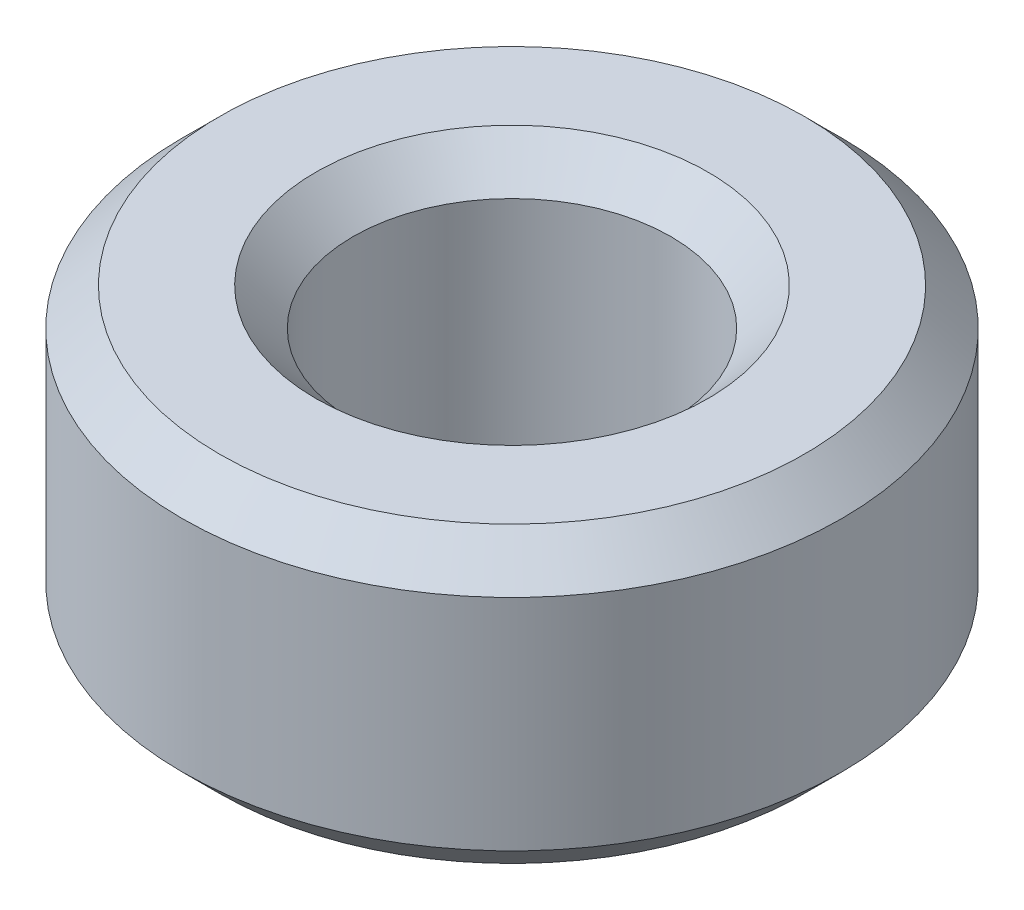
SolidWorks part; units mm, degrees
ref_plane "Front Plane" through (0, 0, 0) normal (0, 0, 1) x (1, 0, 0)
ref_plane "Top Plane" through (0, 0, 0) normal (0, 1, 0) x (1, 0, 0)
ref_plane "Right Plane" through (0, 0, 0) normal (1, 0, 0) x (0, 0, -1)
sketch "Sketch1" plane through (0, 0, 0) normal (0, 1, 0) x (1, 0, 0)
  circle A0 centre (0, 0) radius 12.5
  dimension "SLEEVE_OD" = 25
extrude "Boss-Extrude1" add sketch "Sketch1" along normal blind 11.1429
sketch "Sketch2" plane through (0, 0, 0) normal (0, 1, 0) x (1, 0, 0)
  circle A0 centre (0, 0) radius 6.0251
  dimension "BORE_D" = 12.0502
extrude "Cut-Extrude1" cut sketch "Sketch2" along normal through all
chamfer "Chamfer1" distance 1.4111 angle 45 4 edges at (0, 11.1429, 6.0251) (0, 0, 6.0251) (0, 0, 12.5) (0, 11.1429, 12.5)
